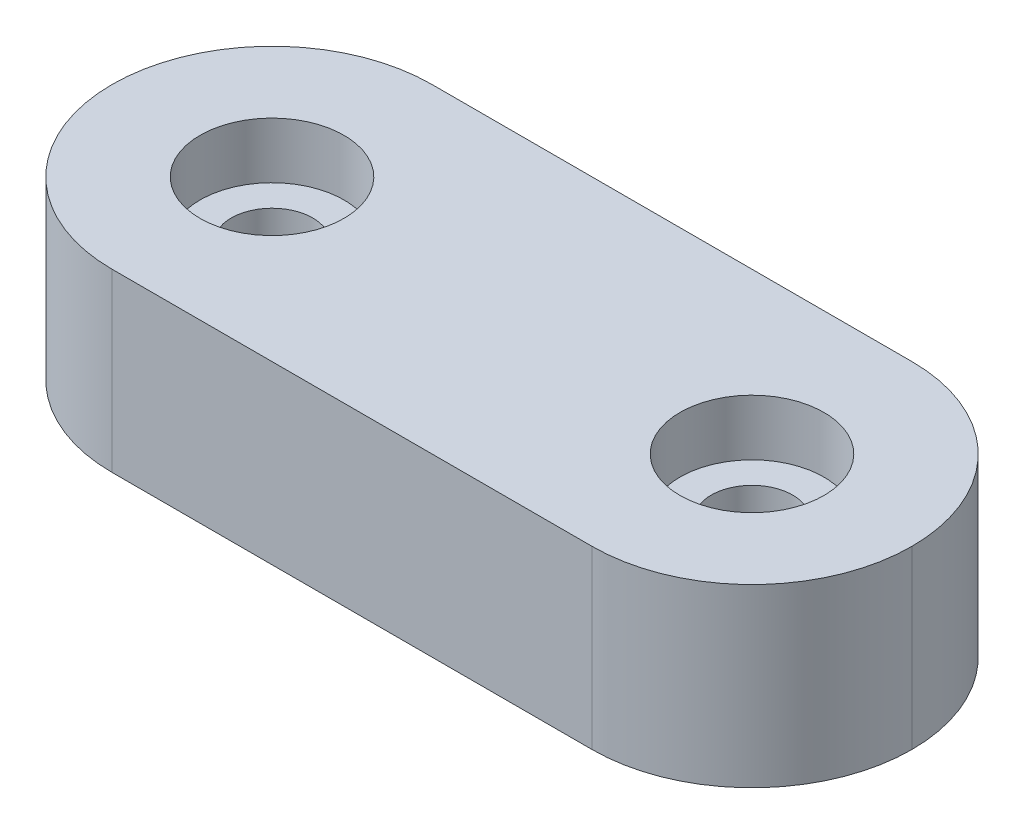
SolidWorks part; units mm, degrees
ref_plane "Спереди" through (0, 0, 0) normal (0, 0, 1) x (1, 0, 0)
ref_plane "Сверху" through (0, 0, 0) normal (0, 1, 0) x (1, 0, 0)
ref_plane "Справа" through (0, 0, 0) normal (1, 0, 0) x (0, 0, -1)
sketch "Эскиз1" plane through (0, 0, 0) normal (0, 1, 0) x (1, 0, 0)
  line L1 (50, -20) -> (-50, -20)
  line L2 (50, -20) -> (50, 20)
  line L3 (50, 20) -> (-50, 20)
  line L4 (-50, -20) -> (-50, 20)
  line L5 (50, -20) -> (-50, 20) construction
  line L6 (50, 20) -> (-50, -20) construction
  point P0 (0, 0)
  dimension "D1" = 40
  dimension "D2" = 100
extrude "Бобышка-Вытянуть1" add sketch "Эскиз1" along normal blind 22
sketch "Эскиз2" plane through (0, 22, 0) normal (0, 1, 0) x (1, 0, 0)
  line L0 (63.3636, 0) -> (-98.8673, 0) construction
  line L1 (-50, 20) -> (-50, -20) construction
  circle A0 centre (-30, 0) radius 4.5497
  circle A1 centre (30, 0) radius 6.3637
  dimension "D1" = 80
  dimension "D2" = 20
hole_wizard "Отверстие обработанное метчиком M121" positions "Трехмерный эскиз1" profile "Эскиз3" tap size "M12" standard "ISO"
sketch3d "Трехмерный эскиз1"
  point P0 (-30, 22, 0)
  point P3 (30, 22, 0)
sketch "Эскиз3" plane through (-30, 22, 0) normal (1, 0, 0) x (0, 0, 1)
  line L0 (0, 0) -> (0, 29.8144)
  line L1 (0, 29.8144) -> (5.1, 26.75)
  line L2 (5.1, 26.75) -> (5.1, 0)
  line L5 (5.1, 0) -> (0, 0)
  line L10 (0, 29.8144) -> (-5.1, 26.75) construction
  line L11 (0, -6.35) -> (0, 107.95) construction
  dimension "Диаметр сверла" = 10.2
  dimension "Глубина сверла" = 26.75
  dimension "Угол заточки сверла" = 118
cosmetic thread "Отверстие резьбы1" parameters "D1"=18, "D2"=12
cosmetic thread "Отверстие резьбы2" parameters "D1"=18, "D2"=12
sketch "Эскиз5" plane through (0, 22, 0) normal (0, 1, 0) x (1, 0, 0)
  circle A0 centre (30, 0) radius 9
  circle A1 centre (-30, 0) radius 9
  dimension "D1" = 18
extrude "Вырез-Вытянуть1" cut sketch "Эскиз5" against normal blind 7
fillet "Скругление1" radius 20 4 edges at (50, 11, 20) (50, 11, -20) (-50, 11, -20) (-50, 11, 20)
